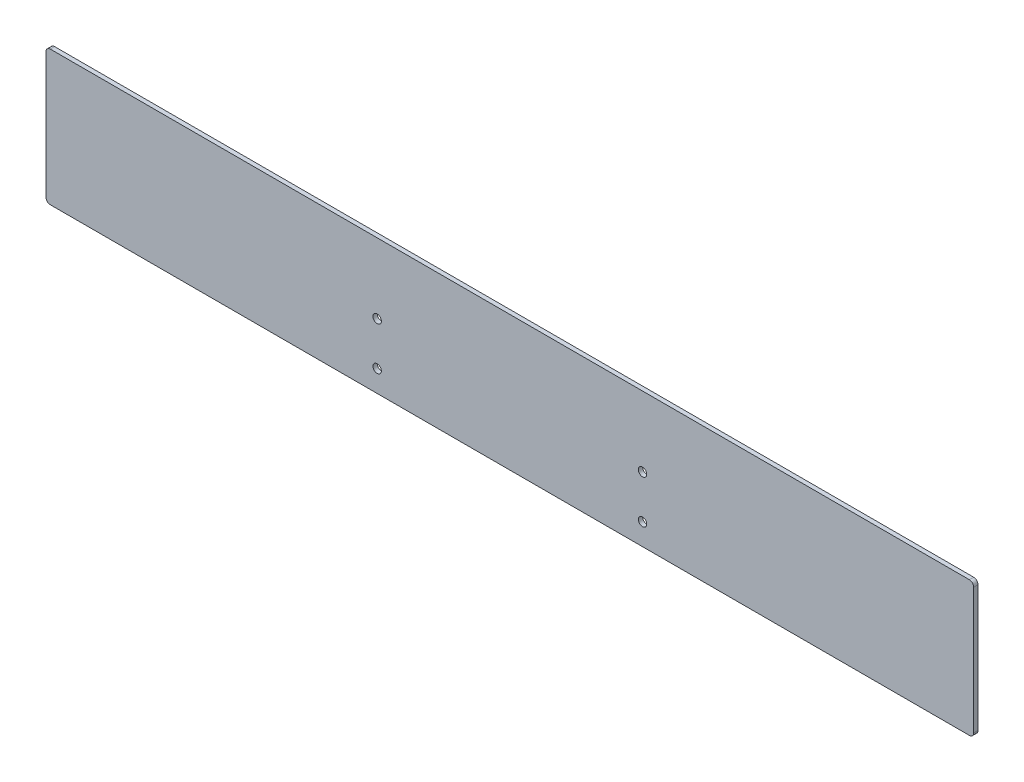
SolidWorks part; units mm, degrees
ref_plane "Front Plane" through (0, 0, 0) normal (0, 0, 1) x (1, 0, 0)
ref_plane "Top Plane" through (0, 0, 0) normal (0, 1, 0) x (1, 0, 0)
ref_plane "Right Plane" through (0, 0, 0) normal (1, 0, 0) x (0, 0, -1)
sketch "Sketch1" plane through (0, 0, 0) normal (0, 0, 1) x (1, 0, 0)
  line L1 (-356.9059, 18.2035) -> (73.0941, 18.2035)
  line L2 (-356.9059, 18.2035) -> (-356.9059, -44.2965)
  line L3 (-356.9059, -44.2965) -> (73.0941, -44.2965)
  line L4 (73.0941, 18.2035) -> (73.0941, -44.2965)
  circle A0 centre (-80.4059, -14.2965) radius 1.95
  circle A1 centre (-80.4059, -34.2965) radius 1.95
  circle A2 centre (-203.4059, -14.2965) radius 1.95
  circle A3 centre (-203.4059, -34.2965) radius 1.95
  dimension "D3" = 123
  dimension "D4" = 20
  dimension "D1" = 430
  dimension "D2" = 62.5
  dimension "D5" = 10
  dimension "D6" = 153.5
extrude "Boss-Extrude1" add sketch "Sketch1" along normal blind 2
fillet "Fillet1" radius 2 4 edges at (73.0941, 18.2035, 1) (73.0941, -44.2965, 1) (-356.9059, -44.2965, 1) (-356.9059, 18.2035, 1)
